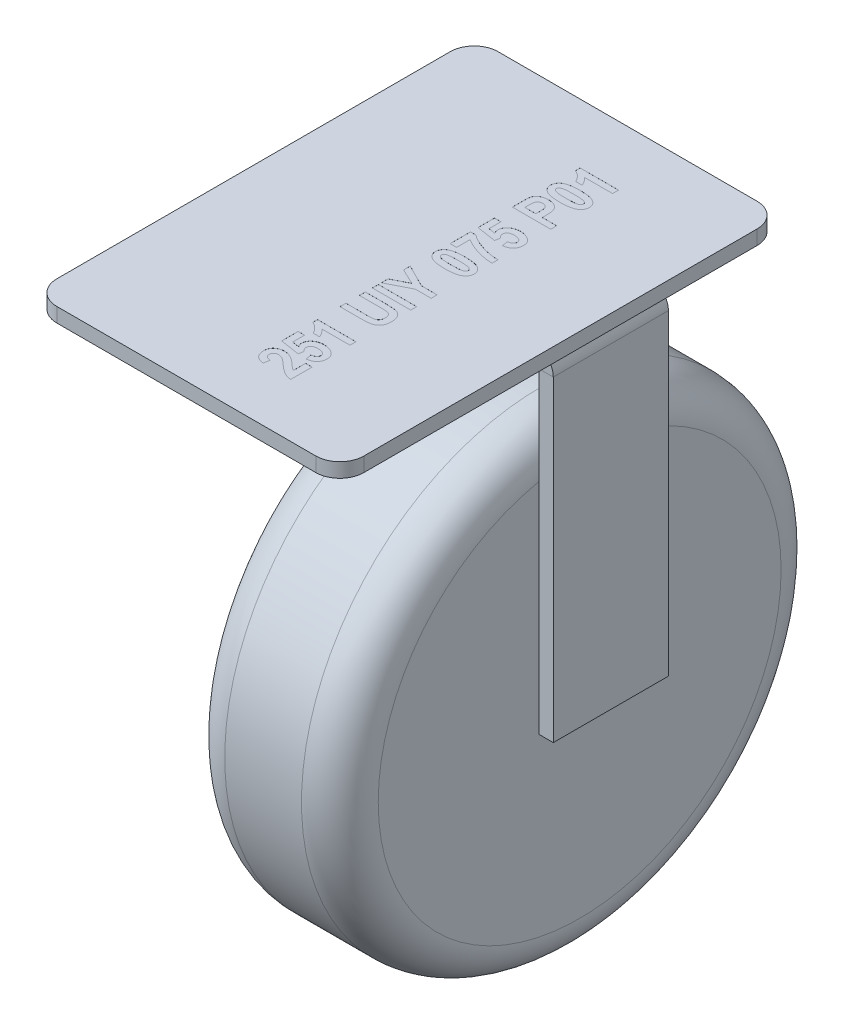
SolidWorks part; units mm, degrees
note: The reader was unsure of these and kept them because the rebuilt part matched: flange length of "Edge-Flange1".
material "Commercially Pure CP-Ti UNS R50400 (SS)"
ref_plane "Front Plane" through (0, 0, 0) normal (0, 0, 1) x (1, 0, 0)
ref_plane "Top Plane" through (0, 0, 0) normal (0, 1, 0) x (1, 0, 0)
ref_plane "Right Plane" through (0, 0, 0) normal (1, 0, 0) x (0, 0, -1)
sketch "Sketch1" plane through (0, 0, 0) normal (1, 0, 0) x (0, 0, -1)
  circle A0 centre (0, 0) radius 50
  dimension "D1" = 100
extrude "Boss-Extrude1" add sketch "Sketch1" along normal mid plane 32
fillet "Fillet1" radius 8 2 edges at (-16, 0, -50) (16, 0, -50)
ref_plane "Plane1" through (0, 80, 0) normal (0, 1, 0) x (-1, 0, 0)
sketch "Sketch2" plane through (0, 80, 0) normal (0, 1, 0) x (-1, 0, 0)
  line L0 (0, 95.4717) -> (0, 0) construction
  line L1 (0, 0) -> (86.2951, 0) construction
  line L2 (-32, 34) -> (32, 34) construction
  line L3 (-32, 80) -> (32, 80)
  line L4 (-32, 80) -> (-32, -12)
  line L5 (-32, -12) -> (32, -12)
  line L6 (32, 80) -> (32, -12)
  dimension "D1" = 64
  dimension "D2" = 92
  dimension "D3" = 34
sheet metal parameters "Sheet-Metal1" thickness 3 parameters "D1"=1
base flange "Base-Flange1" sketch "Sketch2" thickness 3 reverse thickness direction no parameters "D1"=1
ref_plane "Plane2" through (0, 69, 0) normal (0, -1, 0) x (1, 0, 0)
sketch "Sketch4" plane through (0, 69, 0) normal (0, -1, 0) x (1, 0, 0)
  line L0 (0, 80.3203) -> (0, 0) construction
  line L1 (0, 0) -> (65.4763, 0) construction
  line L3 (-22.5, 12) -> (22.5, 12)
  line L4 (-22.5, 12) -> (-22.5, -12)
  line L5 (-22.5, -12) -> (22.5, -12)
  line L6 (22.5, 12) -> (22.5, -12)
  dimension "D1" = 45
  dimension "D2" = 24
sheet metal parameters "Sheet-Metal3" thickness 3 parameters "D1"=1
base flange "Base-Flange2" sketch "Sketch4" thickness 3 reverse thickness direction yes parameters "D1"=1
edge flange "Edge-Flange1" sketch "Sketch10" flange profiles "Sketch10", "Sketch11" flange angle 90 flange length 70 flange position material inside bend radius 1 thickness 3 relief rectangular parameters "D6"=10, "D8"=1
sketch "Sketch10" plane through (22.5, 66, 0) normal (1, 0, 0) x (0, 0, 1)
  line L0 (-12, 0) -> (12, 0) construction
  line L1 (-12, 0) -> (12, 0)
  line L2 (-12, 0) -> (-12, 67)
  line L3 (-12, 67) -> (12, 67)
  line L4 (12, 67) -> (12, 0)
sketch "Sketch11" plane through (-22.5, 66, 0) normal (-1, 0, 0) x (0, 0, -1)
  line L0 (-12, 0) -> (12, 0) construction
  line L1 (-12, 0) -> (12, 0)
  line L2 (-12, 0) -> (-12, 67)
  line L3 (-12, 67) -> (12, 67)
  line L4 (12, 67) -> (12, 0)
bend "EdgeBend1" bend radius 1 bend angle 90 parameters "D5"=1
bend "EdgeBend2" bend radius 1 bend angle 90 parameters "D5"=2
sketch "Sketch13" plane through (0, 69, 0) normal (0, 1, 0) x (1, 0, 0)
  line L0 (0, 0) -> (0, -43.1016) construction
  circle A0 centre (0, -20) radius 23.8799
  dimension "D1" = 20
move or copy body "Body-Move/Copy1" bodies to move or copy 102 copy no translate (0, 0, -19)
move or copy body "Body-Move/Copy2" bodies to move or copy 109 copy no translate (0, 0, 5)
sketch "Sketch18" plane through (0, 80, 0) normal (0, 1, 0) x (1, 0, 0)
  line L0 (10.5466, 26) -> (10.5466, -66) construction
  line L1 (32, 26) -> (-32, 26) construction
  line L2 (-32, -66) -> (32, -66) construction
  text T0 "251 UIY 075 P01" font "Arial Narrow" height 8
extrude "Cut-Extrude2" cut sketch "Sketch18" against normal blind 0.01 normal cut yes
fillet "Fillet9" radius 5 4 edges at (32, 78.5, 66) (-32, 78.5, 66) (32, 78.5, -26) (-32, 78.5, -26)
sketch "Sketch20" plane through (0, 69, 0) normal (0, 1, 0) x (1, 0, 0)
  line L1 (18.5, 12) -> (-18.5, 12)
  line L2 (18.5, 12) -> (18.5, -12)
  line L3 (18.5, -12) -> (-18.5, -12)
  line L4 (-18.5, 12) -> (-18.5, -12)
sketch "Sketch21" plane through (0, 69, 0) normal (0, 1, 0) x (1, 0, 0)
  line L1 (18.5, 12.6378) -> (-18.5, 12.6378)
  line L2 (18.5, 12.6378) -> (18.5, -12.6468)
  line L3 (18.5, -12.6468) -> (-18.5, -12.6468)
  line L4 (-18.5, 12.6378) -> (-18.5, -12.6468)
extrude "Boss-Extrude2" add sketch "Sketch21" along normal blind 10
bend "DerivedBend1" bend radius 1 bend angle 90 parameters "D5"=1
bend "DerivedBend2" bend radius 1 bend angle 90 parameters "D5"=2
flat pattern "Flat-Pattern1" [suppressed]
sketch "Bend-Lines1" plane through (0, 0, 0) normal (0, 1, 0) x (-1, 0, 0)
sketch3d "Bounding-Box1" [suppressed]
  line L0 (0, 0, 0) -> (0, 92, 0) construction
  line L1 (64, 0, 0) -> (64, 92, 0) construction
  line L2 (0, 0, 0) -> (64, 0, 0) construction
  line L3 (0, 92, 0) -> (64, 92, 0) construction
bend of the flat pattern "Flatten-<DerivedBend1>1"
bend of the flat pattern "Flatten-<DerivedBend2>1"
flat pattern "Flat-Pattern3" [suppressed]
sketch "Bend-Lines3" plane through (0, 0, 0) normal (0, 1, 0) x (-1, 0, 0)
bend of the flat pattern "Flatten-<EdgeBend1>2"
bend of the flat pattern "Flatten-<EdgeBend2>2"
